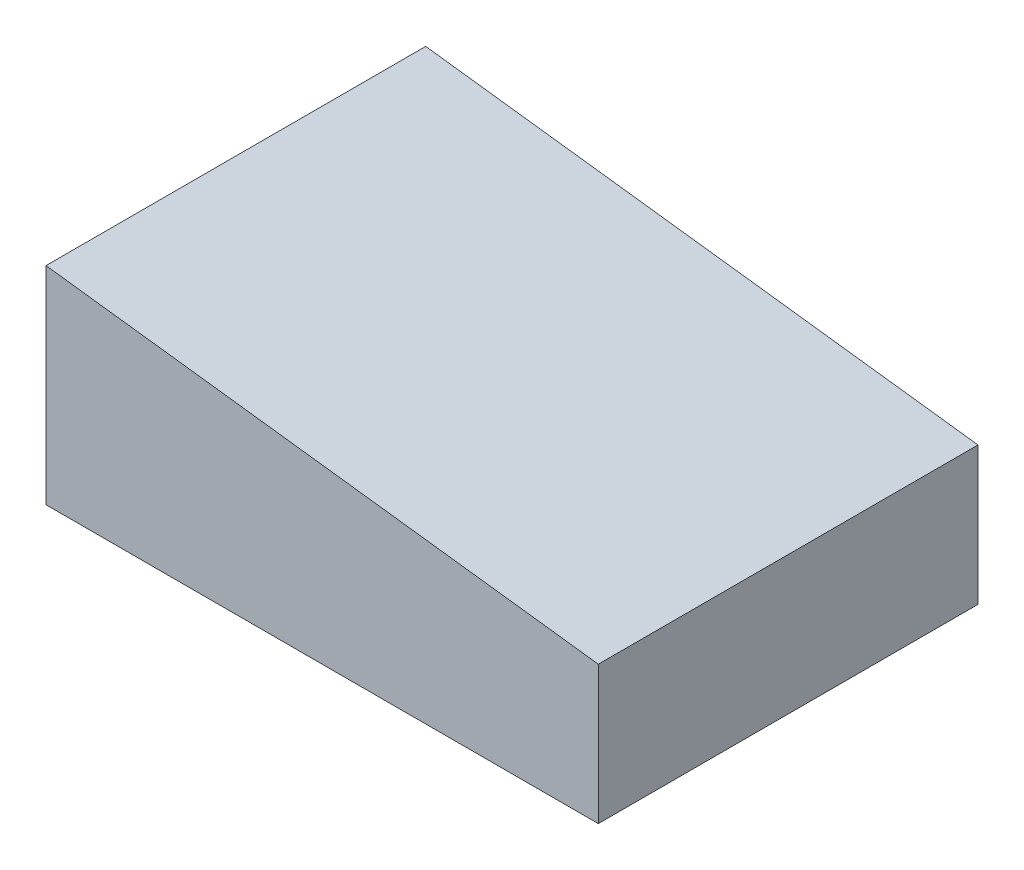
SolidWorks part; units mm, degrees
material "ﾁｰｸ材"
ref_plane "正面" through (0, 0, 0) normal (0, 0, 1) x (1, 0, 0)
ref_plane "平面" through (0, 0, 0) normal (0, 1, 0) x (1, 0, 0)
ref_plane "右側面" through (0, 0, 0) normal (1, 0, 0) x (0, 0, -1)
sketch "ｽｹｯﾁ1" plane through (0, 0, 0) normal (0, 0, 1) x (1, 0, 0)
  line L0 (0, 0) -> (8, 0)
  line L1 (8, 0) -> (8, 2)
  line L2 (8, 2) -> (0, 3)
  line L3 (0, 3) -> (0, 0)
  dimension "D1" = 8
  dimension "D2" = 2
  dimension "D3" = 3
extrude "ﾎﾞｽ - 押し出し1" add sketch "ｽｹｯﾁ1" along normal blind 5.5
